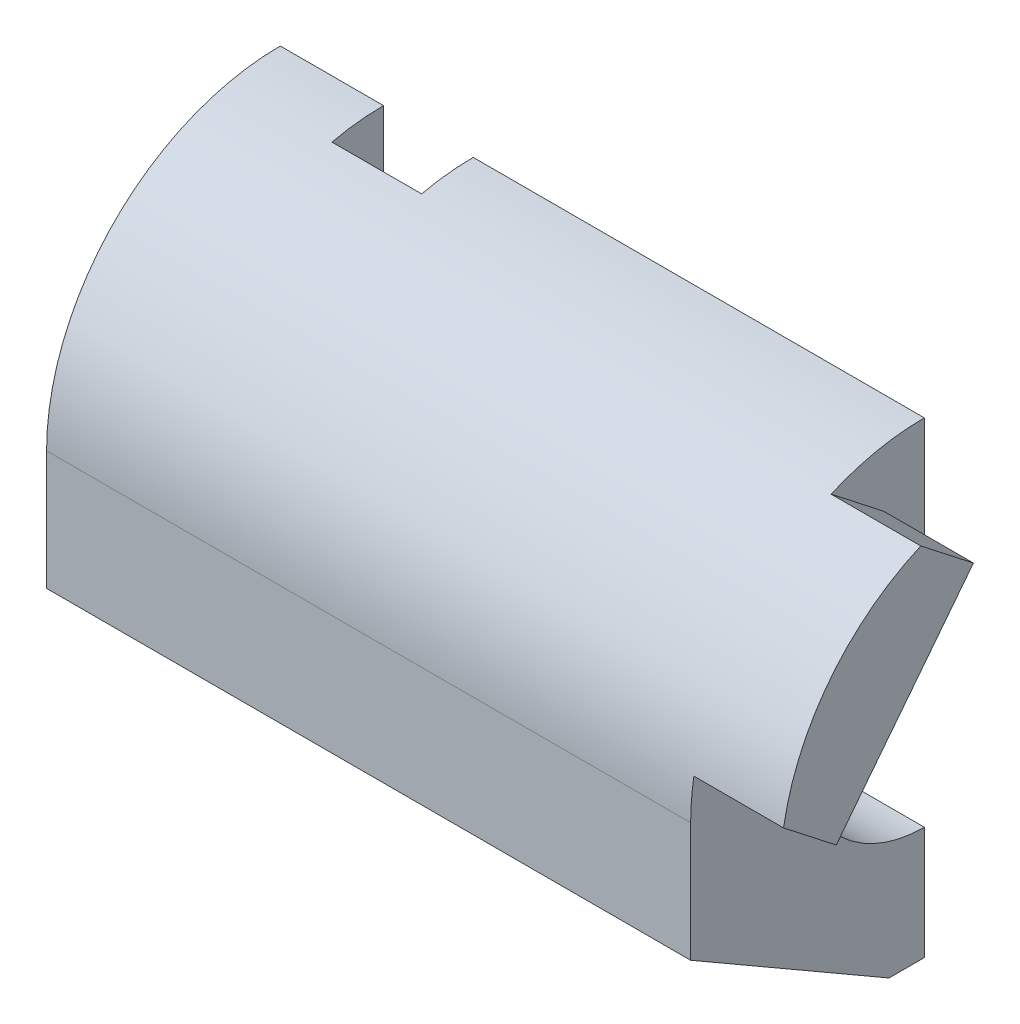
SolidWorks part; units mm, degrees
material "1060 合金"
ref_plane "前视基准面" through (0, 0, 0) normal (0, 0, 1) x (1, 0, 0)
ref_plane "上视基准面" through (0, 0, 0) normal (0, 1, 0) x (1, 0, 0)
ref_plane "右视基准面" through (0, 0, 0) normal (1, 0, 0) x (0, 0, -1)
sketch "草图1" plane through (0, 0, 0) normal (1, 0, 0) x (0, 0, -1)
  line L0 (0, 172) -> (0, 114.575)
  line L1 (0, 0) -> (-13, 0)
  line L5 (-13, 0) -> (-86, 42.1466)
  line L6 (-13, 0) -> (-39.3415, 0) construction
  line L7 (0, 57.425) -> (0, 0)
  line L8 (-86, 42.1466) -> (-86, 86)
  arc A2 (0, 172) -> (-86, 86) centre (0, 86) ccw
  arc A4 (0, 114.575) -> (0, 57.425) centre (0, 86) ccw
  arc A5 (0, 130.45) -> (0, 41.55) centre (0, 86) ccw
  circle A6 centre (0, 86) radius 51 construction
  dimension "D1" = 30
  dimension "D4" = 86
  dimension "D5" = 88.9
  dimension "D3" = 57.15
  dimension "D6" = 86
  dimension "D8" = 102
  dimension "D2" = 13
  dimension "D7" = 86
extrude "凸台-拉伸9" add sketch "草图1" against normal blind 237 contours A4 L7 L1 L5 L8 A2 L0
extrude "切除-拉伸3" cut sketch "草图1<13>" against normal blind 78 contours L0 A5 L7 A4 region at (0, 122.5125, 0.9939)
sketch "草图1<13>" plane through (0, 0, 0) normal (1, 0, 0) x (0, 0, -1) same geometry as "草图1"
sketch "草图10" plane through (0, 0, 0) normal (1, 0, 0) x (0, 0, -1)
  line L0 (-84.8139, 100.2341) -> (-65.4307, 85.0903)
  line L1 (-65.4307, 85.0903) -> (-14.9464, 149.7072)
  line L2 (-14.9464, 149.7072) -> (-34.3296, 164.851)
  line L3 (0, 0) -> (-13, 0) construction
  line L4 (0, 86) -> (-16.0851, 86) construction
  line L5 (0, 86) -> (0, 71.8464) construction
  line L6 (-40.1885, 117.3987) -> (-157.9274, 209.3864) construction
  arc A0 (0, 172) -> (-86, 86) centre (0, 86) ccw construction
  arc A1 (-34.3296, 164.851) -> (-84.8139, 100.2341) centre (0, 86) ccw
  point P16 (0, 0)
  dimension "D1" = 38
  dimension "D2" = 51
  dimension "D3" = 41
  dimension "D4" = 82
  dimension "D5" = 38
  dimension "D6" = 38
ref_plane "基准面4" through (0, 172, 0) normal (0, 1, 0) x (1, 0, 0)
sketch "草图11" plane through (0, 172, 0) normal (0, 1, 0) x (1, 0, 0)
  line L0 (-199, 0) -> (-199, -19)
  line L1 (-237, 0) -> (0, 0) construction
  line L2 (-199, -19) -> (-166, -19)
  line L3 (-166, -19) -> (-166, 0)
  line L4 (-237, 0) -> (-237, -86) construction
  line L5 (-199, 0) -> (-166, 0)
  dimension "D1" = 38
  dimension "D2" = 33
  dimension "D3" = 19
sketch "草图12" plane through (-237, 0, 0) normal (-1, 0, 0) x (0, 0, 1)
  line L0 (0, 57.425) -> (0, 0) construction
  line L1 (0, 15) -> (13, 15)
  line L2 (0, 15) -> (0, 37)
  line L3 (0, 37) -> (13, 37)
  line L4 (13, 15) -> (13, 37)
  line L5 (13, 26) -> (-7.0948, 26) construction
  line L6 (0, 0) -> (13, 0) construction
  point P8 (0, 0)
  dimension "D1" = 26
  dimension "D2" = 13
  dimension "D3" = 22
extrude "切除-拉伸5" cut sketch "草图12" against normal blind 110
sketch "草图13" plane through (0, 0, 0) normal (0, 0, -1) x (-1, 0, 0)
  line L0 (127, 37) -> (127, 15) construction
  circle A0 centre (127, 26) radius 11
extrude "切除-拉伸6" cut sketch "草图13" against normal blind 13
sketch "草图14" plane through (0, 0, 0) normal (0, 0, -1) x (-1, 0, 0)
  line L1 (166, 172) -> (199, 172)
  line L6 (166, 172) -> (166, 108.0345)
  line L8 (199, 108.0345) -> (199, 172)
  line L9 (237, 172) -> (0, 172) construction
  line L10 (237, 172) -> (237, 114.575) construction
  line L12 (166, 108.0345) -> (199, 108.0345)
  dimension "D1" = 38
  dimension "D2" = 33
extrude "切除-拉伸9" cut sketch "草图14" against normal blind 19
extrude "凸台-拉伸11" add sketch "草图10" along normal blind 33
